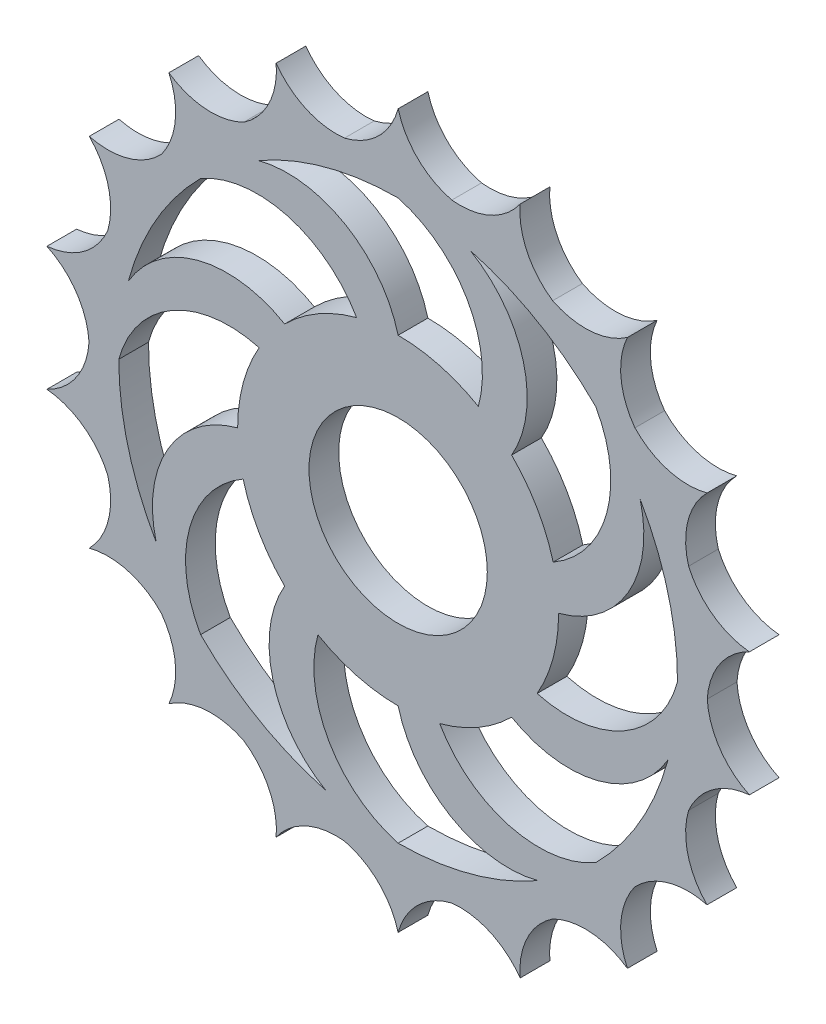
SolidWorks part; units mm, degrees
ref_plane "Alzado" through (0, 0, 0) normal (0, 0, 1) x (1, 0, 0)
ref_plane "Planta" through (0, 0, 0) normal (0, 1, 0) x (1, 0, 0)
ref_plane "Vista lateral" through (0, 0, 0) normal (1, 0, 0) x (0, 0, -1)
sketch "Croquis1" plane through (0, 0, 0) normal (0, 0, 1) x (1, 0, 0)
  line L0 (0, 0) -> (0, 45.345) construction
  line L1 (0, 0) -> (7.766, 44.0431) construction
  line L2 (0, 0) -> (-7.7678, 44.0532) construction
  circle A1 centre (0, 0) radius 33.02
  arc A2 (0, 38.1) -> (-5.7339, 32.5184) centre (-7.5974, 40.1687) cw
  arc A3 (0, 38.1) -> (5.7339, 32.5184) centre (7.5974, 40.1687) ccw
  arc A4 (13.031, 35.8023) -> (16.51, 28.5962) centre (20.8777, 35.1477) ccw
  arc A5 (13.031, 35.8023) -> (5.7339, 32.5184) centre (6.5993, 40.3447) cw
  arc A6 (24.4902, 29.1863) -> (25.2948, 21.2248) centre (31.6399, 25.8875) ccw
  arc A7 (24.4902, 29.1863) -> (16.51, 28.5962) centre (20, 35.6545) cw
  arc A8 (32.9956, 19.05) -> (31.0287, 11.2935) centre (38.5858, 13.5048) ccw
  arc A9 (32.9956, 19.05) -> (25.2948, 21.2248) centre (30.9884, 26.6639) cw
  arc A10 (37.5212, 6.616) -> (33.02, 0) centre (40.8777, -0.5068) ccw
  arc A11 (37.5212, 6.616) -> (31.0287, 11.2935) centre (38.2391, 14.4572) cw
  arc A12 (37.5212, -6.616) -> (31.0287, -11.2935) centre (38.2391, -14.4572) ccw
  arc A13 (37.5212, -6.616) -> (33.02, 0) centre (40.8777, 0.5068) cw
  arc A14 (32.9956, -19.05) -> (25.2948, -21.2248) centre (30.9884, -26.6639) ccw
  arc A15 (32.9956, -19.05) -> (31.0287, -11.2935) centre (38.5858, -13.5048) cw
  arc A16 (24.4902, -29.1863) -> (16.51, -28.5962) centre (20, -35.6545) ccw
  arc A17 (24.4902, -29.1863) -> (25.2948, -21.2248) centre (31.6399, -25.8875) cw
  arc A18 (13.031, -35.8023) -> (5.7339, -32.5184) centre (6.5993, -40.3447) ccw
  arc A19 (13.031, -35.8023) -> (16.51, -28.5962) centre (20.8777, -35.1477) cw
  arc A20 (0, -38.1) -> (-5.7339, -32.5184) centre (-7.5974, -40.1687) ccw
  arc A21 (0, -38.1) -> (5.7339, -32.5184) centre (7.5974, -40.1687) cw
  arc A22 (-13.031, -35.8023) -> (-16.51, -28.5962) centre (-20.8777, -35.1477) ccw
  arc A23 (-13.031, -35.8023) -> (-5.7339, -32.5184) centre (-6.5993, -40.3447) cw
  arc A24 (-24.4902, -29.1863) -> (-25.2948, -21.2248) centre (-31.6399, -25.8875) ccw
  arc A25 (-24.4902, -29.1863) -> (-16.51, -28.5962) centre (-20, -35.6545) cw
  arc A26 (-32.9956, -19.05) -> (-31.0287, -11.2935) centre (-38.5858, -13.5048) ccw
  arc A27 (-32.9956, -19.05) -> (-25.2948, -21.2248) centre (-30.9884, -26.6639) cw
  arc A28 (-37.5212, -6.616) -> (-33.02, 0) centre (-40.8777, 0.5068) ccw
  arc A29 (-37.5212, -6.616) -> (-31.0287, -11.2935) centre (-38.2391, -14.4572) cw
  arc A30 (-37.5212, 6.616) -> (-31.0287, 11.2935) centre (-38.2391, 14.4572) ccw
  arc A31 (-37.5212, 6.616) -> (-33.02, 0) centre (-40.8777, -0.5068) cw
  arc A32 (-32.9956, 19.05) -> (-25.2948, 21.2248) centre (-30.9884, 26.6639) ccw
  arc A33 (-32.9956, 19.05) -> (-31.0287, 11.2935) centre (-38.5858, 13.5048) cw
  arc A34 (-24.4902, 29.1863) -> (-16.51, 28.5962) centre (-20, 35.6545) ccw
  arc A35 (-24.4902, 29.1863) -> (-25.2948, 21.2248) centre (-31.6399, 25.8875) cw
  arc A36 (-13.031, 35.8023) -> (-5.7339, 32.5184) centre (-6.5993, 40.3447) ccw
  arc A37 (-13.031, 35.8023) -> (-16.51, 28.5962) centre (-20.8777, 35.1477) cw
  point P101 (0, 0)
  dimension "D5" = 7.874
  dimension "D2" = 10
  dimension "D3" = 10
  dimension "D6" = 18
extrude "Saliente-Extruir1" add sketch "Croquis1" along normal mid plane 3.175 contours A1 | A34 A35 A1 | A32 A33 A1 | A30 A33 A32 A35 A34 A37 A36 A2 A3 A5 A4 A7 A6 A9 A8 A11 A10 A13 A12 A15 A14 A17 A16 A19 A18 A21 A20 A23 A22 A25 A24 A27 A26 A29 A28 A31 region at (0, 0, 0) region at (-22.0629, 26.2935, 0) region at (-29.7253, 17.1619, 0)
sketch "Croquis2" plane through (0, 0, 1.5875) normal (0, 0, 1) x (1, 0, 0)
  line L0 (0, 0) -> (0, 38.1) construction
  line L1 (0, 0) -> (14.9225, 25.8465) construction
  line L2 (0, 0) -> (-4.7625, 8.2489) construction
  line L3 (-8.5725, 14.848) -> (-14.9225, 25.8465) construction
  circle A0 centre (0, 0) radius 9.525
  arc A3 (8.5725, 14.848) -> (0, 17.145) centre (0, 0) ccw
  arc A4 (0, 29.845) -> (-14.9225, 25.8465) centre (0, 0) ccw
  arc A5 (-14.9225, 25.8465) -> (0, 17.145) centre (-11.812, 14.0345) cw
  arc A6 (0, 29.845) -> (8.5725, 14.848) centre (-3.2122, 18.0603) cw
  arc A7 (21.1036, 21.1036) -> (7.7245, 28.8281) centre (0, 0) ccw
  arc A8 (7.7245, 28.8281) -> (12.1233, 12.1233) centre (1.5715, 18.2763) cw
  arc A9 (16.5608, 4.4375) -> (12.1233, 12.1233) centre (0, 0) ccw
  arc A10 (21.1036, 21.1036) -> (16.5608, 4.4375) centre (10.4991, 15.0419) cw
  arc A11 (29.845, 0) -> (25.8465, 14.9225) centre (0, 0) ccw
  arc A12 (25.8465, 14.9225) -> (17.145, 0) centre (14.0345, 11.812) cw
  arc A13 (14.848, -8.5725) -> (17.145, 0) centre (0, 0) ccw
  arc A14 (29.845, 0) -> (14.848, -8.5725) centre (18.0603, 3.2122) cw
  arc A15 (21.1036, -21.1036) -> (28.8281, -7.7245) centre (0, 0) ccw
  arc A16 (28.8281, -7.7245) -> (12.1233, -12.1233) centre (18.2763, -1.5715) cw
  arc A17 (4.4375, -16.5608) -> (12.1233, -12.1233) centre (0, 0) ccw
  arc A18 (21.1036, -21.1036) -> (4.4375, -16.5608) centre (15.0419, -10.4991) cw
  arc A19 (0, -29.845) -> (14.9225, -25.8465) centre (0, 0) ccw
  arc A20 (14.9225, -25.8465) -> (0, -17.145) centre (11.812, -14.0345) cw
  arc A21 (-8.5725, -14.848) -> (0, -17.145) centre (0, 0) ccw
  arc A22 (0, -29.845) -> (-8.5725, -14.848) centre (3.2122, -18.0603) cw
  arc A23 (-21.1036, -21.1036) -> (-7.7245, -28.8281) centre (0, 0) ccw
  arc A24 (-7.7245, -28.8281) -> (-12.1233, -12.1233) centre (-1.5715, -18.2763) cw
  arc A25 (-16.5608, -4.4375) -> (-12.1233, -12.1233) centre (0, 0) ccw
  arc A26 (-21.1036, -21.1036) -> (-16.5608, -4.4375) centre (-10.4991, -15.0419) cw
  arc A27 (-29.845, 0) -> (-25.8465, -14.9225) centre (0, 0) ccw
  arc A28 (-25.8465, -14.9225) -> (-17.145, 0) centre (-14.0345, -11.812) cw
  arc A29 (-14.848, 8.5725) -> (-17.145, 0) centre (0, 0) ccw
  arc A30 (-29.845, 0) -> (-14.848, 8.5725) centre (-18.0603, -3.2122) cw
  arc A31 (-21.1036, 21.1036) -> (-28.8281, 7.7245) centre (0, 0) ccw
  arc A32 (-28.8281, 7.7245) -> (-12.1233, 12.1233) centre (-18.2763, 1.5715) cw
  arc A33 (-4.4375, 16.5608) -> (-12.1233, 12.1233) centre (0, 0) ccw
  arc A34 (-21.1036, 21.1036) -> (-4.4375, 16.5608) centre (-15.0419, 10.4991) cw
  point P61 (0, 0)
  dimension "D1" = 19.05
  dimension "D5" = 34.29
  dimension "D2" = 59.69
  dimension "D3" = 30
  dimension "D4" = 30
  dimension "D6" = 8
extrude "Cortar-Extruir1" cut sketch "Croquis2" against normal through all
ref_axis "Eje1" through (-41.2733, 0, 0) along (1, 0, 0)
sketch "Croquis4" plane through (0, 0, 0) normal (0, 0, 1) x (1, 0, 0)
  circle A2 centre (0, 0) radius 33.655
  dimension "D1" = 67.31
